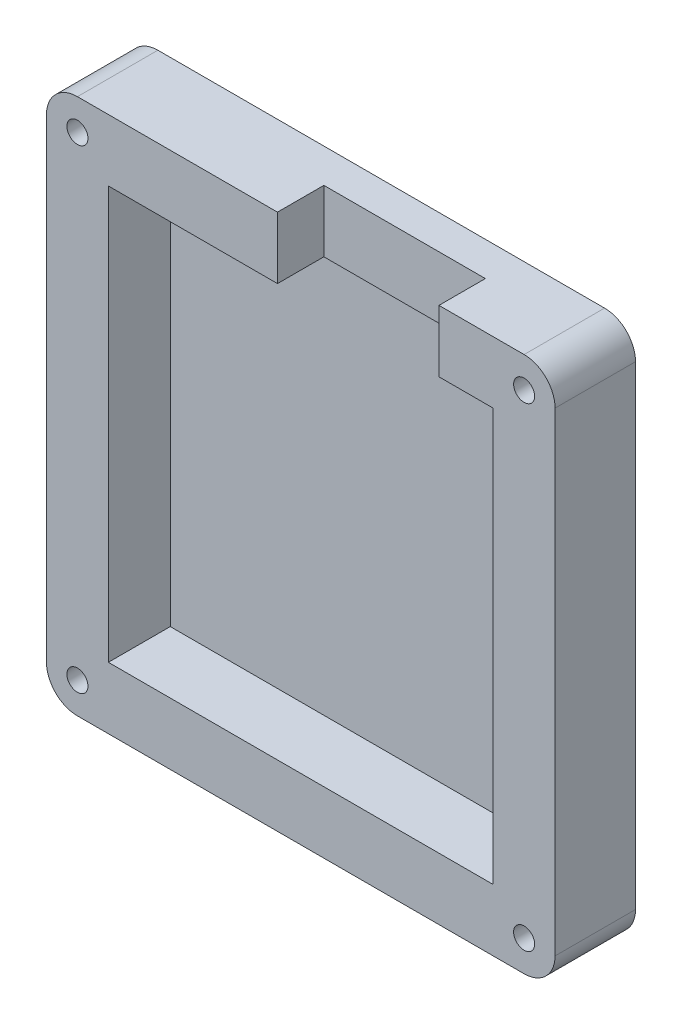
SolidWorks part; units mm, degrees
ref_plane "Front Plane" through (0, 0, 0) normal (0, 0, 1) x (1, 0, 0)
ref_plane "Top Plane" through (0, 0, 0) normal (0, 1, 0) x (1, 0, 0)
ref_plane "Right Plane" through (0, 0, 0) normal (1, 0, 0) x (0, 0, -1)
sketch "Sketch2" plane through (0, 0, 0) normal (0, 0, 1) x (1, 0, 0)
  line L1 (31.0965, 33.3375) -> (-31.0965, 33.3375)
  line L2 (31.0965, 33.3375) -> (31.0965, -33.3375)
  line L3 (31.0965, -33.3375) -> (-31.0965, -33.3375)
  line L4 (-31.0965, 33.3375) -> (-31.0965, -33.3375)
  line L5 (31.0965, 33.3375) -> (-31.0965, -33.3375) construction
  line L6 (31.0965, -33.3375) -> (-31.0965, 33.3375) construction
  line L7 (-41.0965, 43.3375) -> (41.0965, 43.3375)
  line L8 (-41.0965, 43.3375) -> (-41.0965, -43.3375)
  line L9 (-41.0965, -43.3375) -> (41.0965, -43.3375)
  line L10 (41.0965, 43.3375) -> (41.0965, -43.3375)
  circle A5 centre (36.0965, 38.3375) radius 1.7
  circle A6 centre (-36.0965, -38.3375) radius 1.7
  circle A7 centre (36.0965, -38.3375) radius 1.7
  circle A8 centre (-36.0965, 38.3375) radius 1.7
  circle A9 centre (-36.0965, 38.3375) radius 3
  circle A10 centre (36.0965, 38.3375) radius 3
  circle A11 centre (-36.0965, -38.3375) radius 3
  circle A12 centre (36.0965, -38.3375) radius 3
  point P0 (0, 0)
  dimension "D8" = 5
  dimension "D9" = 3.4
  dimension "D10" = 5
  dimension "D12" = 3.4
  dimension "D13" = 3.4
  dimension "D14" = 5
  dimension "D15" = 5
  dimension "D16" = 3.4
  dimension "D17" = 5
  dimension "D18" = 5
  dimension "D19" = 6
  dimension "D20" = 6
  dimension "D21" = 6
  dimension "D22" = 6
  dimension "D1" = 62.193
  dimension "D2" = 66.675
  dimension "D3" = 10
  dimension "D4" = 10
  dimension "D5" = 10
  dimension "D6" = 10
  dimension "D7" = 5
  dimension "D11" = 5
  dimension "D23" = 82.193
  dimension "D24" = 86.675
extrude "Boss-Extrude4" add sketch "Sketch2" along normal blind 9.9 from offset 3.1 contours A5 | A10 | A9 | A6 | A11 | A7 | A12 | A8
extrude "Boss-Extrude5" add sketch "Sketch2<12>" along normal blind 13 contours L10 L7 L8 L9 A12 A11 A10 A9 L4 L1 L2 L3 region at (0, 42.143, 0)
sketch "Sketch2<12>" plane through (0, 0, 0) normal (0, 0, 1) x (1, 0, 0) same geometry as "Sketch2"
ref_plane "Plane1" through (-31.0965, -33.3375, 13) normal (0, -1, 0) x (-1, 0, 0)
extrude "Boss-Extrude6" add sketch "Sketch2<13>" along normal blind 3 contours L1 L4 L3 L2 region at (0, 0, 0)
sketch "Sketch2<13>" plane through (0, 0, 0) normal (0, 0, 1) x (1, 0, 0) same geometry as "Sketch2"
sketch "Sketch5" plane through (0, 0, 13) normal (0, 0, 1) x (1, 0, 0)
  line L0 (-41.0965, 43.3375) -> (41.0965, 43.3375) construction
  line L1 (-3.7665, 43.3375) -> (22.3313, 43.3375)
  line L2 (-3.7665, 43.3375) -> (-3.7665, 33.3375)
  line L3 (-3.7665, 33.3375) -> (22.3313, 33.3375)
  line L4 (22.3313, 43.3375) -> (22.3313, 33.3375)
  line L5 (31.0965, 33.3375) -> (-31.0965, 33.3375) construction
  line L6 (-31.0965, 33.3375) -> (-31.0965, -33.3375) construction
  dimension "D1" = 26.0978
  dimension "D2" = 27.33
extrude "Cut-Extrude1" cut sketch "Sketch5" against normal blind 7.5 contours L2 L3 L4 L1
fillet "Fillet1" radius 5 4 edges at (-41.0965, -43.3375, 6.5) (-41.0965, 43.3375, 6.5) (41.0965, -43.3375, 6.5) (41.0965, 43.3375, 6.5)
ref_plane "Plane24" through (-41.0965, -38.3375, 13) normal (0, -1, 0) x (-1, 0, 0)
sketch "Sketch7" plane through (0, 0, 0) normal (0, 0, -1) x (-1, 0, 0)
  text T0 "darsh's tetrios" font "Century Gothic" height in points 8
  point P1 (-1.5934, -4.428)
  point P2 (0, 0)
  dimension "D1" = 0
extrude "Cut-Extrude2" cut sketch "Sketch7" against normal blind 0.2
